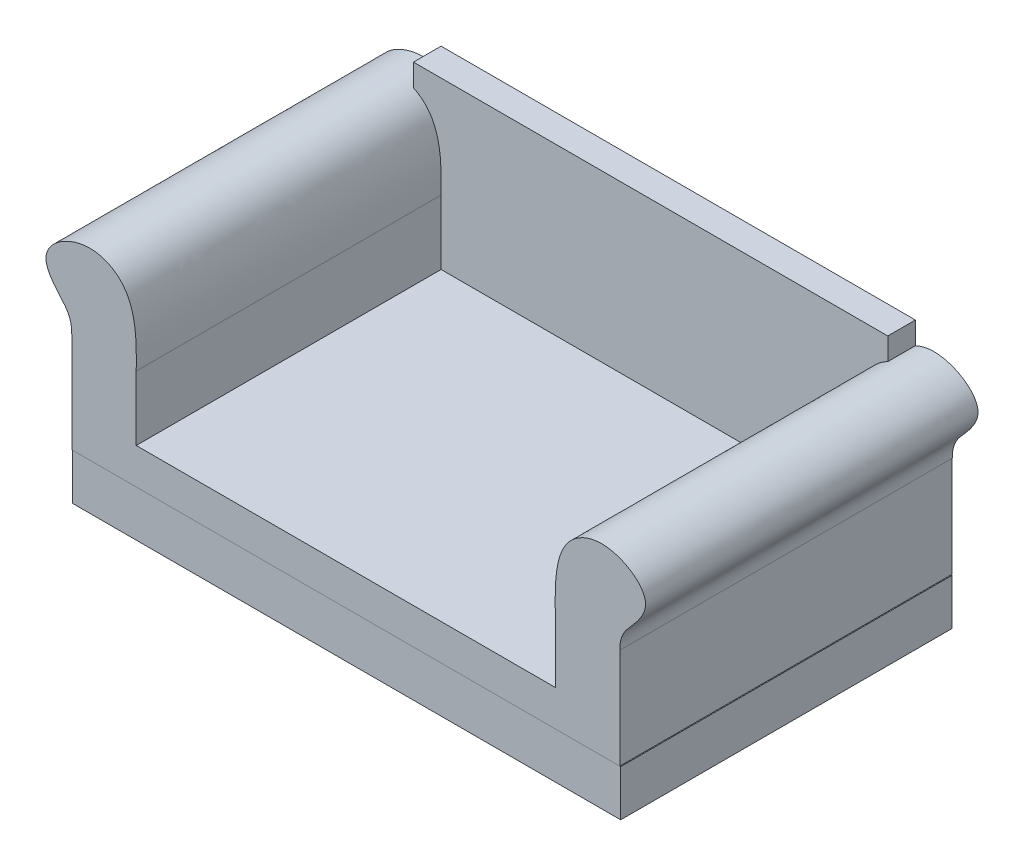
SolidWorks part; units mm, degrees
ref_plane "Front Plane" through (0, 0, 0) normal (0, 0, 1) x (1, 0, 0)
ref_plane "Top Plane" through (0, 0, 0) normal (0, 1, 0) x (1, 0, 0)
ref_plane "Right Plane" through (0, 0, 0) normal (1, 0, 0) x (0, 0, -1)
sketch "Sketch1" plane through (0, 0, 0) normal (0, 1, 0) x (1, 0, 0)
  line L1 (-755.65, -457.2) -> (755.65, -457.2) construction
  line L2 (-755.65, -457.2) -> (-755.65, 457.2) construction
  line L3 (-755.65, 457.2) -> (755.65, 457.2) construction
  line L4 (755.65, -457.2) -> (755.65, 457.2) construction
  line L5 (-755.65, -457.2) -> (755.65, 457.2) construction
  line L6 (-755.65, 457.2) -> (755.65, -457.2) construction
  line L7 (-755.65, 457.2) -> (-666.75, 457.2)
  line L8 (-755.65, 457.2) -> (-755.65, -457.2)
  line L9 (-755.65, -457.2) -> (-666.75, -457.2)
  line L10 (-666.75, 457.2) -> (-666.75, -457.2)
  line L11 (-711.2, -457.2) -> (-711.2, 457.2) construction
  line L12 (-755.65, 0) -> (-666.75, 0) construction
  line L13 (666.75, 457.2) -> (755.65, 457.2)
  line L14 (666.75, 457.2) -> (666.75, -457.2)
  line L15 (666.75, -457.2) -> (755.65, -457.2)
  line L16 (755.65, 457.2) -> (755.65, -457.2)
  line L17 (711.2, -457.2) -> (711.2, 457.2) construction
  line L18 (666.75, 0) -> (755.65, 0) construction
  line L19 (-666.75, 431.8) -> (666.75, 431.8)
  line L20 (-666.75, 431.8) -> (-666.75, 457.2)
  line L21 (-666.75, 457.2) -> (666.75, 457.2)
  line L22 (666.75, 431.8) -> (666.75, 457.2)
  line L23 (0, 457.2) -> (0, 431.8) construction
  line L24 (-666.75, 444.5) -> (666.75, 444.5) construction
  line L25 (-666.75, -457.2) -> (666.75, -457.2)
  line L26 (-666.75, -457.2) -> (-666.75, -431.8)
  line L27 (-666.75, -431.8) -> (666.75, -431.8)
  line L28 (666.75, -457.2) -> (666.75, -431.8)
  line L29 (0, -431.8) -> (0, -457.2) construction
  line L30 (-666.75, -444.5) -> (666.75, -444.5) construction
  line L31 (31.75, 431.8) -> (57.15, 431.8)
  line L32 (31.75, 431.8) -> (31.75, -431.8)
  line L33 (31.75, -431.8) -> (57.15, -431.8)
  line L34 (57.15, 431.8) -> (57.15, -431.8)
  line L35 (44.45, -431.8) -> (44.45, 431.8) construction
  line L36 (31.75, 0) -> (57.15, 0) construction
  point P0 (0, 0)
  point P140 (711.2, 0)
  point P190 (44.45, 0)
  point P309 (0, -444.5)
  point P335 (0, 444.5)
  point P376 (-711.2, 0)
  dimension "D1" = 914.4
  dimension "D3" = 88.9
  dimension "D4" = 25.4
  dimension "D5" = 25.4
  dimension "D6" = 25.4
  dimension "D7" = 787.4
  dimension "D2" = 698.5
extrude "Boss-Extrude1" add sketch "Sketch1" along normal blind 127 contours L10 L7 L8 L9 | L27 L10 L25 L14 | L16 L13 L14 L15 | L21 L10 L19 L14 | L34 L19 L32 L27 region at (-711.2, 0, 0) region at (0, 0, -444.5) region at (711.2, 0, 0) region at (0, 0, 444.5) region at (44.45, 0, 0)
ref_plane "Plane1" through (0, 129.54, 0) normal (0, 1, 0) x (1, 0, 0)
sketch "Sketch2" plane through (0, 129.54, 0) normal (0, 1, 0) x (1, 0, 0)
  line L0 (755.65, 457.2) -> (755.65, -457.2) construction
  line L1 (-755.65, -457.2) -> (755.65, -457.2) construction
  line L2 (-755.65, 457.2) -> (-755.65, -457.2) construction
  line L3 (-755.65, 457.2) -> (755.65, 457.2) construction
  line L4 (755.65, 457.2) -> (755.65, -457.2)
  line L5 (-755.65, -457.2) -> (755.65, -457.2)
  line L6 (-755.65, 457.2) -> (-755.65, -457.2)
  line L7 (-755.65, 457.2) -> (755.65, 457.2)
ref_plane "Plane2" through (0, 0, 459.74) normal (0, 0, 1) x (1, 0, 0)
sketch "Sketch4" plane through (0, 0, 459.74) normal (0, 0, 1) x (1, 0, 0)
  line L0 (-755.65, 129.54) -> (755.65, 129.54) construction
  line L4 (-755.65, 0) -> (755.65, 0) construction
  line L5 (755.65, 0) -> (755.65, 127) construction
  line L6 (755.65, 127) -> (-755.65, 127) construction
  line L7 (-755.65, 127) -> (-755.65, 0) construction
  line L8 (-755.65, 129.54) -> (755.65, 129.54)
  line L12 (-755.65, 0) -> (755.65, 0)
  line L13 (755.65, 0) -> (755.65, 127)
  line L14 (755.65, 127) -> (-755.65, 127)
  line L15 (-755.65, 127) -> (-755.65, 0)
  line L16 (-755.65, 129.54) -> (-755.65, 406.4)
  line L17 (-577.85, 406.4) -> (-577.85, 228.6)
  line L18 (-577.85, 228.6) -> (577.85, 228.6)
  line L19 (0, 0) -> (0, 50000) construction
  line L20 (577.85, 406.4) -> (577.85, 228.6)
  line L21 (755.65, 129.54) -> (755.65, 406.4)
  spline S0 degree 3 poles (-755.65, 406.4) (-755.65, 451.0873) (-791.2169, 477.4334) (-855.3989, 573.8525) (-720.3037, 663.2325) (-568.8677, 589.8389) (-577.85, 447.6507) (-577.85, 406.4) knots 0 0 0 0 0.157243 0.266643 0.492649 0.701572 1 1 1 1
  spline S1 degree 3 poles (755.65, 406.4) (755.65, 451.0873) (791.2169, 477.4334) (855.3989, 573.8525) (720.3037, 663.2325) (568.8677, 589.8389) (577.85, 447.6507) (577.85, 406.4) knots 0 0 0 0 0.157243 0.266643 0.492649 0.701572 1 1 1 1
  point P47 (0, 228.6)
  dimension "D1" = 635
  dimension "D2" = 406.4
  dimension "D3" = 228.6
  dimension "D4" = 177.8
extrude "Boss-Extrude3" add sketch "Sketch4" against normal up to surface (916.94 mm away) separate body contours S0 L17 L18 L20 S1 L21 L8 L16 up to face at (0, 63.5, -457.2)
sketch "Sketch5" plane through (0, 228.6, 0) normal (0, 1, 0) x (1, 0, 0)
  line L0 (-755.65, 457.2) -> (755.65, 457.2) construction
  line L1 (-654.05, 457.2) -> (654.05, 457.2)
  line L2 (-654.05, 457.2) -> (-654.05, 381)
  line L3 (-654.05, 381) -> (654.05, 381)
  line L4 (577.85, 457.2) -> (-577.85, 457.2)
  line L5 (-577.85, 457.2) -> (-577.85, -459.74)
  line L6 (-577.85, -459.74) -> (577.85, -459.74)
  line L7 (577.85, -459.74) -> (577.85, 457.2)
  line L8 (577.85, 457.2) -> (-577.85, 457.2)
  line L9 (-577.85, 457.2) -> (-577.85, -459.74)
  line L10 (-577.85, -459.74) -> (577.85, -459.74)
  line L11 (577.85, -459.74) -> (577.85, 457.2)
  line L12 (654.05, 457.2) -> (654.05, 381)
  line L13 (0, 381) -> (0, 457.2) construction
  line L14 (-654.05, 419.1) -> (654.05, 419.1) construction
  point P112 (0, 419.1)
  dimension "D2" = 76.2
  dimension "D3" = 76.2
  dimension "D1" = 0
extrude "Boss-Extrude4" add sketch "Sketch5" along normal blind 457.2 contours L1 L12 L3 L2
equation "\"D5@Sketch1\"=\"D4@Sketch1\""
